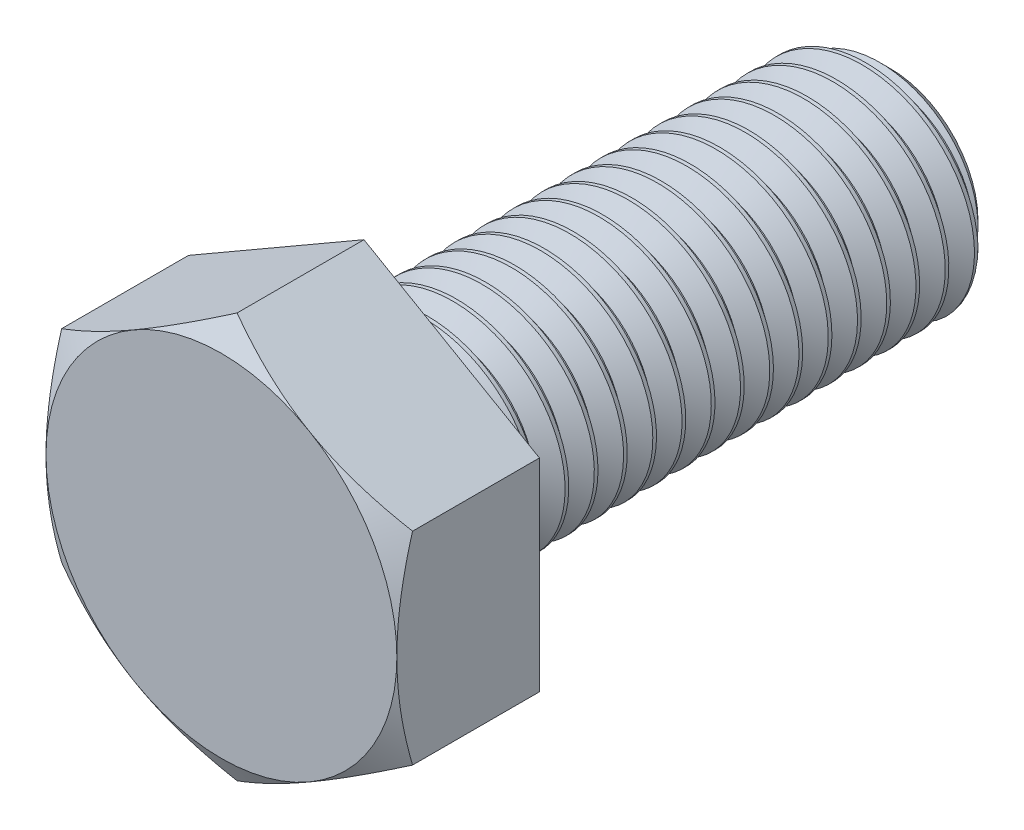
SolidWorks part; units mm, degrees
ref_plane "Front Plane" through (0, 0, 0) normal (0, 0, 1) x (1, 0, 0)
ref_plane "Top Plane" through (0, 0, 0) normal (0, 1, 0) x (1, 0, 0)
ref_plane "Right Plane" through (0, 0, 0) normal (1, 0, 0) x (0, 0, -1)
sketch "Sketch1" plane through (0, 0, 0) normal (1, 0, 0) x (0, 0, -1)
  line L0 (0, 0) -> (19.05, 0) construction
  line L1 (19.05, 3.9688) -> (19.05, -3.9688) construction
  line L2 (0, 6.35) -> (0, -6.35) construction
  line L3 (0, 0) -> (-5.1594, 0) construction
  line L4 (-5.1594, 6.35) -> (-5.1594, -6.35) construction
  line L5 (18.9839, 4.0833) -> (20.0422, 4.0833) construction
  line L6 (20.0422, 4.0833) -> (19.513, 3.1668) construction
  line L7 (19.513, 3.1668) -> (18.9839, 4.0833) construction
  line L8 (19.0169, 4.026) -> (20.0091, 4.026) construction
  line L9 (19.05, 3.9688) -> (19.976, 3.9688) construction
  line L10 (19.4469, 3.2813) -> (19.5792, 3.2813) construction
  line L11 (19.513, 4.0833) -> (19.513, 3.9688) construction
  line L12 (19.513, 3.2813) -> (19.513, 3.1668) construction
  point P5 (19.05, 0)
  point P9 (0, 0)
  point P13 (-5.1594, 0)
  point P18 (16.4042, -3.9688)
  point P25 (19.513, 4.026)
  dimension "Length" = 19.05
  dimension "Thread OD" = 7.9375
  dimension "Hex Width" = 12.7
  dimension "Hex Height" = 5.1594
  dimension "D1" = 60
  dimension "Pitch" = 1.0583
  dimension "D2" = 0.1323
  dimension "D3" = 2.6458
sketch "Sketch2" plane through (0, 0, 0) normal (1, 0, 0) x (0, 0, -1)
  line L0 (0, 0) -> (19.05, 0)
  line L1 (0, 6.35) -> (0, -6.35) construction
  line L2 (19.05, 0) -> (19.05, 3.9688)
  line L3 (19.05, 3.9688) -> (0, 3.9687)
  line L4 (0, 3.9687) -> (0, 0)
revolve "Revolve1" add sketch "Sketch2" angle 360 about L0
sketch "Sketch3" plane through (0, 0, 0) normal (0, 0, 1) x (1, 0, 0)
  line L1 (0, 7.3323) -> (-6.35, 3.6662)
  line L2 (-6.35, 3.6662) -> (-6.35, -3.6662)
  line L3 (-6.35, -3.6662) -> (0, -7.3323)
  line L4 (0, -7.3323) -> (6.35, -3.6662)
  line L5 (6.35, -3.6662) -> (6.35, 3.6662)
  line L6 (6.35, 3.6662) -> (0, 7.3323)
  circle A0 centre (0, 0) radius 6.35 construction
extrude "Boss-Extrude1" add sketch "Sketch3" along normal up to vertex (5.1594 mm away) up to point (0, 0, 5.1594)
chamfer "Chamfer1" distance 0.7938 angle 45 1 edges at (3.9688, 0, -19.05)
sketch "Sketch4" plane through (0, 0, 5.1594) normal (0, 0, 1) x (1, 0, 0)
  circle A0 centre (0, 0) radius 6.35
extrude "Cut-Extrude1" cut sketch "Sketch4" against normal through all draft 60 flip side to cut
ref_axis "Center Axis 1" through (0, 0, -68.7678) along (0, 0, 1)
split "Split1" bodies to split 106 resulting bodies 107 108 split by face at (3.9687, 0, 0)
sketch "Sketch5" plane through (0, 0, 0) normal (1, 0, 0) x (0, 0, -1)
  line L0 (19.0169, 4.026) -> (20.0091, 4.026)
  line L1 (19.0169, 4.026) -> (19.4469, 3.2813)
  line L2 (19.4469, 3.2813) -> (19.5792, 3.2813)
  line L3 (20.0091, 4.026) -> (19.5792, 3.2813)
sketch "Sketch6" plane through (0, 0, -19.05) normal (0, 0, -1) x (-1, 0, 0)
  circle A0 centre (0, 0) radius 3.9688
curve "Helix/Spiral1" pitch 1.0583 height 20.1083 radius 3.9688 centre (0, 0, -19.05) axis (0, 0, 1) start towards (0, 1, 0)
sweep "Cut-Sweep1" cut profiles "Sketch5" path "Helix/Spiral1" align with end faces yes
combine bodies "Combine1" operation type add bodies to combine 108 109
equation "\"D2@Sketch1\"=\"Pitch@Sketch1\"/8"
equation "\"D1@Chamfer1\"=\"Pitch@Sketch1\"*.75"
equation "\"D4@Helix/Spiral1\"=\"Pitch@Sketch1\""
equation "\"D3@Helix/Spiral1\"=\"Length@Sketch1\"+\"Pitch@Sketch1\""
equation "\"D3@Sketch1\"=\"Pitch@Sketch1\"*2.5"
